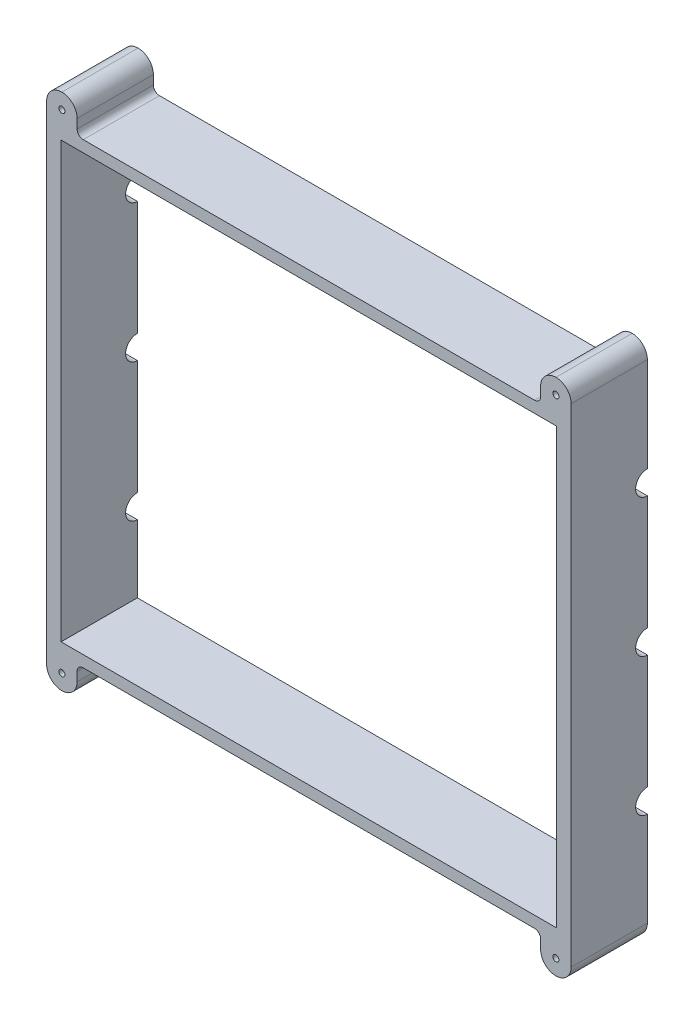
SolidWorks part; units mm, degrees
ref_plane "Front Plane" through (0, 0, 0) normal (0, 0, 1) x (1, 0, 0)
ref_plane "Top Plane" through (0, 0, 0) normal (0, 1, 0) x (1, 0, 0)
ref_plane "Right Plane" through (0, 0, 0) normal (1, 0, 0) x (0, 0, -1)
sketch "Sketch1" plane through (0, 0, 0) normal (0, 0, 1) x (1, 0, 0)
  line L1 (-109.22, -95.25) -> (109.22, -95.25)
  line L2 (-109.22, -95.25) -> (-109.22, 95.25)
  line L3 (-109.22, 95.25) -> (109.22, 95.25)
  line L4 (109.22, -95.25) -> (109.22, 95.25)
  line L5 (-109.22, -95.25) -> (109.22, 95.25) construction
  line L6 (-109.22, 95.25) -> (109.22, -95.25) construction
  point P0 (0, 0)
  dimension "D1" = 218.44
  dimension "D2" = 190.5
extrude "Boss-Extrude1" add sketch "Sketch1" along normal blind 31.75
sketch "Sketch2" plane through (0, 0, 31.75) normal (0, 0, 1) x (1, 0, 0)
  line L1 (-103.1875, -90.4875) -> (103.1875, -90.4875)
  line L2 (-103.1875, -90.4875) -> (-103.1875, 90.4875)
  line L3 (-103.1875, 90.4875) -> (103.1875, 90.4875)
  line L4 (103.1875, -90.4875) -> (103.1875, 90.4875)
  line L5 (-103.1875, -90.4875) -> (103.1875, 90.4875) construction
  line L6 (-103.1875, 90.4875) -> (103.1875, -90.4875) construction
  point P0 (0, 0)
  dimension "D1" = 206.375
  dimension "D2" = 180.975
extrude "Cut-Extrude1" cut sketch "Sketch2" against normal through all
sketch "Sketch3" plane through (109.22, 0, 0) normal (1, 0, 0) x (0, 0, -1)
  line L0 (0, -95.25) -> (0, 95.25) construction
  circle A0 centre (0, 0) radius 4.8895
  circle A1 centre (0, 57.404) radius 4.8895
  circle A2 centre (0, -57.404) radius 4.8895
  point P9 (0, 0)
  point P10 (0, 0)
  dimension "D1" = 9.779
  dimension "D2" = 9.779
  dimension "D3" = 9.779
  dimension "D4" = 57.404
  dimension "D5" = 57.404
extrude "Cut-Extrude2" cut sketch "Sketch3" against normal through all
sketch "Sketch4" plane through (0, 0, 0) normal (0, 0, -1) x (-1, 0, 0)
  line L1 (-109.22, 95.25) -> (-96.52, 95.25)
  line L2 (-109.22, 95.25) -> (-109.22, 107.95)
  line L3 (-109.22, 107.95) -> (-96.52, 107.95)
  line L4 (-96.52, 95.25) -> (-96.52, 107.95)
  dimension "D1" = 12.7
  dimension "D2" = 12.7
extrude "Boss-Extrude2" add sketch "Sketch4" against normal through all
sketch "Sketch5" plane through (0, 0, 31.75) normal (0, 0, 1) x (1, 0, 0)
  line L0 (96.52, 101.6) -> (109.22, 101.6) construction
  line L3 (102.87, 107.95) -> (102.87, 95.25) construction
  line L6 (109.22, 107.95) -> (109.22, -95.25) construction
  line L7 (96.52, 107.95) -> (109.22, 107.95) construction
  circle A0 centre (102.87, 101.6) radius 1.27
  dimension "D4" = 2.54
  dimension "D1" = 6.35
  dimension "D2" = 6.35
  dimension "D3" = 6.35
extrude "Cut-Extrude3" cut sketch "Sketch5" against normal through all
fillet "Fillet1" radius 6.35 2 edges at (96.52, 107.95, 15.875) (109.22, 107.95, 15.875)
sketch "Sketch6" plane through (0, 0, 0) normal (0, 0, -1) x (-1, 0, 0)
  line L1 (-109.22, -95.25) -> (-96.52, -95.25)
  line L2 (-109.22, -95.25) -> (-109.22, -107.95)
  line L3 (-109.22, -107.95) -> (-96.52, -107.95)
  line L4 (-96.52, -95.25) -> (-96.52, -107.95)
  circle A0 centre (-102.87, -101.6) radius 1.27
  dimension "D5" = 2.54
  dimension "D1" = 12.7
  dimension "D2" = 12.7
  dimension "D3" = 6.35
  dimension "D4" = 6.35
extrude "Boss-Extrude3" add sketch "Sketch6" against normal through all
fillet "Fillet4" radius 6.35 2 edges at (109.22, -107.95, 15.875) (96.52, -107.95, 15.875)
mirror "Mirror8" about plane through (0, 0, 0) normal (1, 0, 0) of "Fillet4", "Boss-Extrude3", "Fillet1", "Cut-Extrude3", "Boss-Extrude2"
fillet "Fillet5" radius 2.54 4 edges at (96.52, -95.25, 15.875) (-96.52, -95.25, 15.875) (96.52, 95.25, 15.875) (-96.52, 95.25, 15.875)
